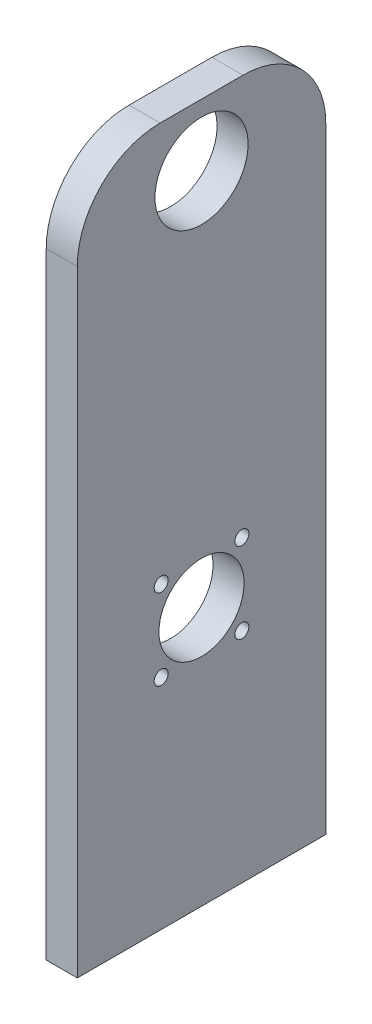
SolidWorks part; units mm, degrees
ref_plane "Front Plane" through (0, 0, 0) normal (0, 0, 1) x (1, 0, 0)
ref_plane "Top Plane" through (0, 0, 0) normal (0, 1, 0) x (1, 0, 0)
ref_plane "Right Plane" through (0, 0, 0) normal (1, 0, 0) x (0, 0, -1)
sketch "Sketch1" plane through (0, 0, 0) normal (0, 1, 0) x (1, 0, 0)
  line L1 (-4.7625, 38.1) -> (4.7625, 38.1)
  line L2 (-4.7625, 38.1) -> (-4.7625, -38.1)
  line L3 (-4.7625, -38.1) -> (4.7625, -38.1)
  line L4 (4.7625, 38.1) -> (4.7625, -38.1)
  line L5 (-4.7625, 38.1) -> (4.7625, -38.1) construction
  line L6 (-4.7625, -38.1) -> (4.7625, 38.1) construction
  point P0 (0, 0)
  dimension "D1" = 76.2
  dimension "D2" = 9.525
extrude "Boss-Extrude1" add sketch "Sketch1" along normal mid plane 214.376
sketch "Sketch3" plane through (-4.7625, 0, 0) normal (-1, 0, 0) x (0, 0, 1)
  line L0 (-45.1772, -15.4437) -> (44.4211, -15.4437) construction
  line L1 (-45.1772, -40.1878) -> (44.4211, -40.1878) construction
  line L2 (-38.1, 107.188) -> (38.1, 107.188) construction
  line L3 (-45.1772, -27.813) -> (44.4211, -27.813) construction
  line L4 (-12.3658, -8.7664) -> (-12.3658, -58.1325) construction
  line L5 (12.3748, -8.7664) -> (12.3748, -58.1325) construction
  line L6 (0, -8.7664) -> (0, -58.1325) construction
  circle A0 centre (0, 88.138) radius 14.2875
  circle A1 centre (-12.3658, -15.4437) radius 2.1463
  circle A2 centre (12.3748, -15.4437) radius 2.1463
  circle A3 centre (-12.3658, -40.1878) radius 2.1463
  circle A4 centre (12.3748, -40.1878) radius 2.1463
  circle A5 centre (0, -27.813) radius 13.0556
  point P12 (-38.1, 107.188)
  dimension "D1" = 28.575
  dimension "D2" = 19.05
  dimension "D3" = 12.3658
  dimension "D4" = 12.3748
  dimension "D7" = 26.1112
  dimension "D8" = 4.2926
  dimension "D5" = 12.3693
  dimension "D6" = 12.3748
  dimension "D9" = 24.7406
extrude "Cut-Extrude2" cut sketch "Sketch3" against normal blind 45.974
fillet "Fillet1" radius 25.4 2 edges at (0, 107.188, 38.1) (0, 107.188, -38.1)
sketch "Sketch4" plane through (-4.7625, 0, 0) normal (-1, 0, 0) x (0, 0, 1)
  line L0 (-38.1, 81.788) -> (-38.1, -107.188) construction
  circle A0 centre (-1.5, 11.3124) radius 2.5
  circle A1 centre (-1.5, -54.6876) radius 2.5
  circle A2 centre (0, -21.6876) radius 7.9248
  dimension "D4" = 36.6
  dimension "D5" = 5
  dimension "D2" = 15.8496
  dimension "D1" = 66
  dimension "D3" = 33
  dimension "D6" = 1.5
  dimension "D7" = 1.5
  dimension "D8" = 38.1
extrude "Cut-Extrude3" [suppressed] cut sketch "Sketch4" against normal through all
